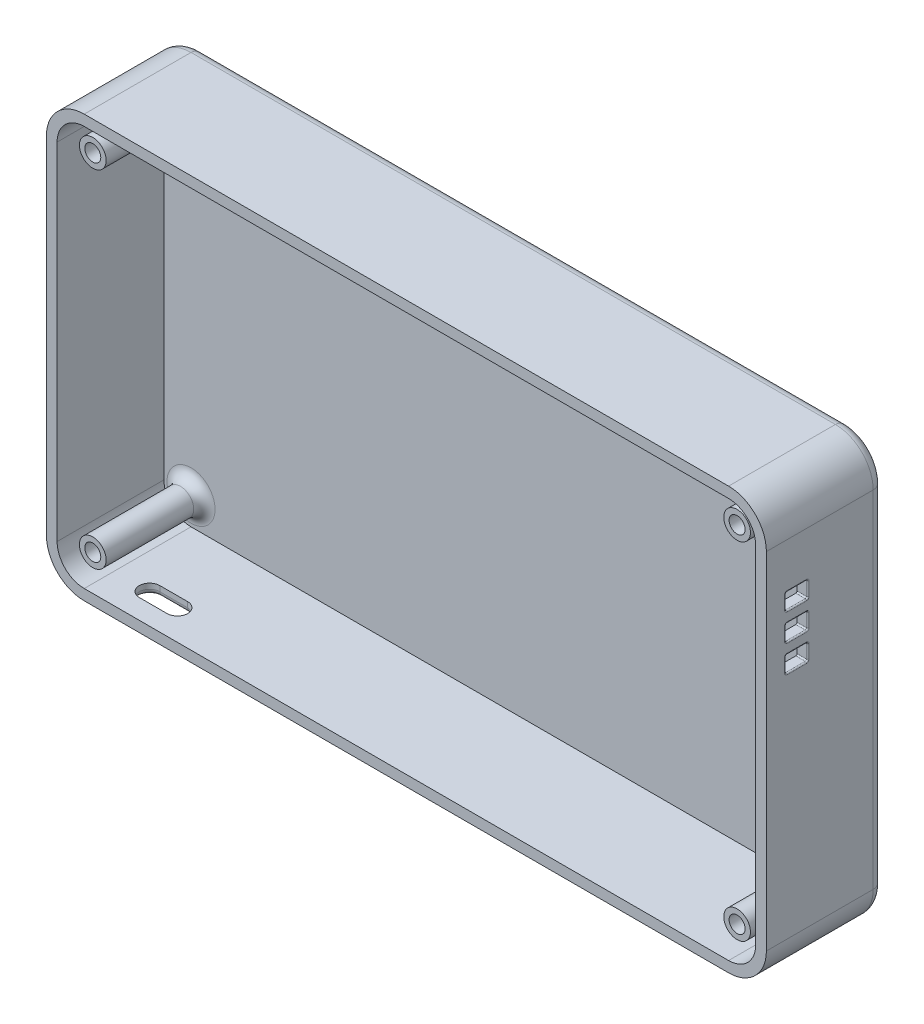
SolidWorks part; units mm, degrees
material "Plastique personnalisé"
ref_plane "Plan de face" through (0, 0, 0) normal (0, 0, 1) x (1, 0, 0)
ref_plane "Plan de dessus" through (0, 0, 0) normal (0, 1, 0) x (1, 0, 0)
ref_plane "Plan de droite" through (0, 0, 0) normal (1, 0, 0) x (0, 0, -1)
sketch "Esquisse1" plane through (0, 0, 0) normal (0, 0, 1) x (1, 0, 0)
  line L0 (33.02, -40.64) -> (153.67, -40.64)
  line L1 (158.75, -45.72) -> (158.75, -110.49)
  line L2 (153.67, -115.57) -> (33.02, -115.57)
  line L3 (27.94, -110.49) -> (27.94, -45.72)
  arc A0 (27.94, -45.72) -> (33.02, -40.64) centre (33.02, -45.72) cw
  arc A1 (153.67, -40.64) -> (158.75, -45.72) centre (153.67, -45.72) cw
  arc A2 (158.75, -110.49) -> (153.67, -115.57) centre (153.67, -110.49) cw
  arc A3 (33.02, -115.57) -> (27.94, -110.49) centre (33.02, -110.49) cw
  circle A8 centre (153.67, -110.49) radius 2.4984
  circle A9 centre (33.02, -110.49) radius 2.5
  circle A10 centre (153.67, -45.72) radius 2.5
  circle A11 centre (33.02, -45.72) radius 2.5
extrude "Boss.-Extru.1" add sketch "Esquisse1" along normal blind 20
shell "Coque1" thickness 2 removed face at (93.345, -78.105, 20) outward yes
fillet "Congé1" radius 2 8 edges at (93.345, -117.57, -2) (28.0137, -115.4963, -2) (25.94, -78.105, -2) (28.0137, -40.7137, -2) (93.345, -38.64, -2) (158.6763, -40.7137, -2) (160.75, -78.105, -2) (158.6763, -115.4963, -2)
sketch "Esquisse2" plane through (0, 0, 20) normal (0, 0, 1) x (1, 0, 0)
  circle A0 centre (153.67, -110.49) radius 1.5
  circle A1 centre (33.02, -110.49) radius 1.5
  circle A2 centre (33.02, -45.72) radius 1.5
  circle A3 centre (153.67, -45.72) radius 1.5
extrude "Enlèv. mat.-Extru.1" cut sketch "Esquisse2" against normal blind 15
fillet "Congé2" radius 2 4 edges at (35.52, -45.72, 0) (156.17, -45.72, 0) (35.52, -110.49, 0) (156.1684, -110.49, 0)
ref_plane "Plan1" through (0, 0, 18.4) normal (0, 0, 1) x (1, 0, 0)
sketch "Esquisse6" plane through (0, 0, 18.4) normal (0, 0, 1) x (1, 0, 0)
  circle A0 centre (153.67, -110.49) radius 2.4984
  circle A1 centre (33.02, -110.49) radius 2.5
  circle A2 centre (33.02, -45.72) radius 2.5
  circle A3 centre (153.67, -45.72) radius 2.5
extrude "Enlèv. mat.-Extru.2" cut sketch "Esquisse6" along normal blind 15
sketch "Esquisse7" plane through (0, -117.57, 0) normal (0, -1, 0) x (1, 0, 0)
  line L0 (39.6272, 14.3718) -> (44.8328, 14.3718) construction
  line L1 (39.6272, 16.3022) -> (44.8328, 16.3022)
  line L2 (39.6272, 12.4415) -> (44.8328, 12.4415)
  arc A0 (42.4237, 14.2215) -> (42.0363, 14.2215) centre (42.23, 14.1718) ccw construction
  arc A1 (39.6272, 16.3022) -> (39.6272, 12.4415) centre (39.6272, 14.3718) ccw
  arc A2 (44.8328, 12.4415) -> (44.8328, 16.3022) centre (44.8328, 14.3718) ccw
  point P5 (42.23, 14.3718)
extrude "Enlèv. mat.-Extru.3" cut sketch "Esquisse7" against normal blind 10
fillet "Congé3" radius 1 4 edges at (42.23, -117.57, 12.4415) (37.6969, -117.57, 14.3718) (42.23, -117.57, 16.3022) (46.7631, -117.57, 14.3718)
sketch "Esquisse9" plane through (160.75, 0, 0) normal (1, 0, 0) x (0, 0, -1)
  line L1 (-16.35, -67.38) -> (-12.25, -67.38)
  line L2 (-16.35, -67.38) -> (-16.35, -64.38)
  line L3 (-16.35, -64.38) -> (-12.25, -64.38)
  line L4 (-12.25, -67.38) -> (-12.25, -64.38)
  line L5 (-16.35, -62.3) -> (-12.25, -62.3)
  line L6 (-16.35, -62.3) -> (-16.35, -59.3)
  line L7 (-16.35, -59.3) -> (-12.25, -59.3)
  line L8 (-12.25, -62.3) -> (-12.25, -59.3)
  line L9 (-16.35, -57.22) -> (-12.25, -57.22)
  line L10 (-16.35, -57.22) -> (-16.35, -54.22)
  line L11 (-16.35, -54.22) -> (-12.25, -54.22)
  line L12 (-12.25, -57.22) -> (-12.25, -54.22)
extrude "Enlèv. mat.-Extru.4" cut sketch "Esquisse9" against normal blind 10
fillet "Congé4" radius 0.25 24 edges at (159.75, -67.38, 16.35) (159.75, -67.38, 12.25) (159.75, -64.38, 12.25) (159.75, -64.38, 16.35) (159.75, -59.3, 16.35) (159.75, -62.3, 16.35) (159.75, -59.3, 12.25) (159.75, -62.3, 12.25) (159.75, -57.22, 12.25) (159.75, -57.22, 16.35) (159.75, -54.22, 16.35) (159.75, -54.22, 12.25) (160.75, -55.72, 12.25) (160.75, -57.22, 14.3) (160.75, -54.22, 14.3) (160.75, -55.72, 16.35) (160.75, -60.8, 16.35) (160.75, -59.3, 14.3) (160.75, -62.3, 14.3) (160.75, -60.8, 12.25) (160.75, -65.88, 12.25) (160.75, -65.88, 16.35) (160.75, -67.38, 14.3) (160.75, -64.38, 14.3)
sketch "Esquisse10" plane through (0, 0, -2) normal (0, 0, -1) x (-1, 0, 0)
  circle A0 centre (-154.305, -65.88) radius 2.4
  circle A1 centre (-154.305, -60.8) radius 2.4
  circle A2 centre (-154.305, -55.72) radius 2.4
extrude "Enlèv. mat.-Extru.5" cut sketch "Esquisse10" against normal blind 10
fillet "Congé5" radius 0.25 3 edges at (151.905, -55.72, -2) (151.905, -60.8, -2) (151.905, -65.88, -2)
ref_plane "symetrieA" through (0, -78.105, 0) normal (0, 1, 0) x (1, 0, 0)
ref_plane "symetrieB" through (93.345, 0, 0) normal (1, 0, 0) x (0, 0, -1)
